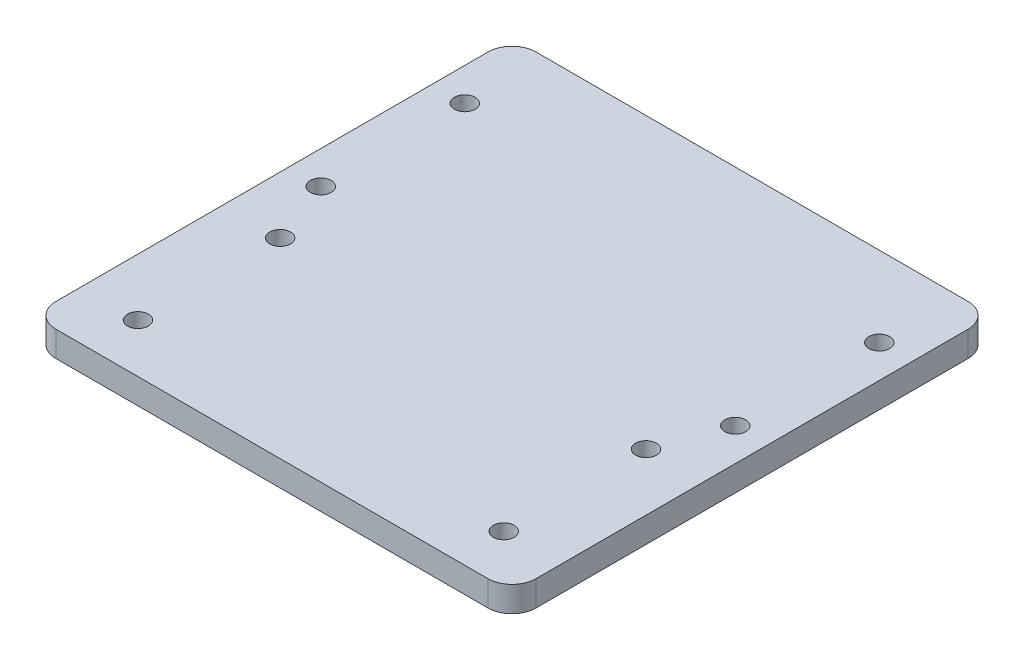
SolidWorks part; units mm, degrees
ref_plane "Front Plane" through (0, 0, 0) normal (0, 0, 1) x (1, 0, 0)
ref_plane "Top Plane" through (0, 0, 0) normal (0, 1, 0) x (1, 0, 0)
ref_plane "Right Plane" through (0, 0, 0) normal (1, 0, 0) x (0, 0, -1)
sketch "Sketch1" plane through (0, 0, 0) normal (0, 1, 0) x (1, 0, 0)
  line L1 (-30, 30) -> (30, 30)
  line L2 (-30, 30) -> (-30, -30)
  line L3 (-30, -30) -> (30, -30)
  line L4 (30, 30) -> (30, -30)
  line L5 (-30, 30) -> (30, -30) construction
  line L6 (-30, -30) -> (30, 30) construction
  point P0 (0, 0)
  dimension "D1" = 60
  dimension "D2" = 60
extrude "Boss-Extrude1" add sketch "Sketch1" along normal blind 3.175
sketch "Sketch2" plane through (0, 3.175, 0) normal (0, 1, 0) x (1, 0, 0)
  line L0 (0, 30) -> (0, -30) construction
  line L1 (30, 30) -> (-30, 30) construction
  line L2 (-30, -30) -> (30, -30) construction
  line L3 (-30, 30) -> (-30, -30) construction
  circle A0 centre (-25.9, 20) radius 1.3
  circle A1 centre (-25.9, 2) radius 1.3
  circle A2 centre (25.9, 2) radius 1.3
  circle A3 centre (25.9, 20) radius 1.3
  point P11 (-24.6, 20)
  point P17 (24.6, 20)
  dimension "D1" = 2.6
  dimension "D2" = 18
  dimension "D3" = 5.4
  dimension "D4" = 10
extrude "Cut-Extrude1" cut sketch "Sketch2" against normal up to surface (3.175 mm away) up to face at (0, 0, 0)
fillet "Fillet1" radius 3 4 edges at (-30, 1.5875, 30) (30, 1.5875, 30) (30, 1.5875, -30) (-30, 1.5875, -30)
sketch "Sketch3" plane through (0, 3.175, 0) normal (0, 1, 0) x (1, 0, 0)
  line L1 (-22.86, -6.11) -> (22.86, -6.11) construction
  line L2 (-22.86, -6.11) -> (-22.86, -23.89) construction
  line L3 (-22.86, -23.89) -> (22.86, -23.89) construction
  line L4 (22.86, -6.11) -> (22.86, -23.89) construction
  line L5 (-22.86, -6.11) -> (22.86, -23.89) construction
  line L6 (-22.86, -23.89) -> (22.86, -6.11) construction
  circle A0 centre (-22.86, -6.11) radius 1.3
  circle A1 centre (22.86, -6.11) radius 1.3
  circle A2 centre (22.86, -23.89) radius 1.3
  circle A3 centre (-22.86, -23.89) radius 1.3
  point P0 (0, -15)
  point P9 (0, 0)
  dimension "D1" = 2.6
  dimension "D2" = 45.72
  dimension "D3" = 17.78
  dimension "D4" = 15
extrude "Cut-Extrude2" cut sketch "Sketch3" against normal up to surface (3.175 mm away) up to face at (25.9, 0, -18.7)
